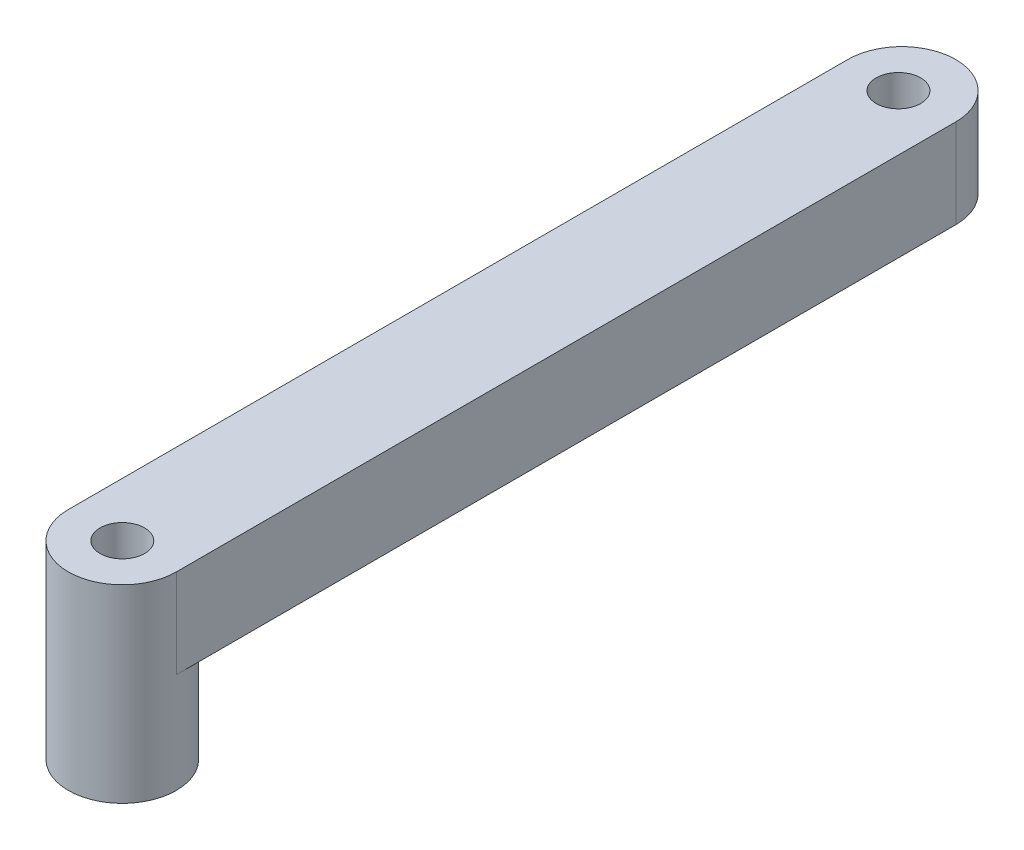
SolidWorks part; units mm, degrees
material "ABS"
ref_plane "Front Plane" through (0, 0, 0) normal (0, 0, 1) x (1, 0, 0)
ref_plane "Top Plane" through (0, 0, 0) normal (0, 1, 0) x (1, 0, 0)
ref_plane "Right Plane" through (0, 0, 0) normal (1, 0, 0) x (0, 0, -1)
sketch "Sketch1" plane through (0, 0, 0) normal (0, 1, 0) x (1, 0, 0)
  circle A0 centre (0, 0) radius 4.85
  circle A1 centre (0, 0) radius 2
  dimension "D1" = 9.7
  dimension "D2" = 4
extrude "Boss-Extrude1" add sketch "Sketch1" along normal blind 9
sketch "Sketch2" plane through (0, 9, 0) normal (0, 1, 0) x (1, 0, 0)
  line L0 (-4.85, 0) -> (-4.85, 70)
  line L2 (4.85, 70) -> (4.85, 0)
  circle A0 centre (0, 0) radius 4.85 construction
  arc A1 (-4.85, 70) -> (4.85, 70) centre (0, 70) cw
  arc A2 (-4.85, 0) -> (4.85, 0) centre (0, 0) ccw
  dimension "D1" = 70
extrude "Boss-Extrude2" add sketch "Sketch2" along normal blind 8
sketch "Sketch4" plane through (0, 9, 0) normal (0, -1, 0) x (1, 0, 0)
  circle A0 centre (0, 0) radius 2
extrude "Cut-Extrude1" cut sketch "Sketch4" against normal blind 10
sketch "Sketch5" plane through (0, 17, 0) normal (0, 1, 0) x (1, 0, 0)
  line L0 (4.85, 0) -> (4.85, 70) construction
  circle A0 centre (-0.15, 69.8523) radius 2
  arc A1 (4.85, 70) -> (-4.85, 70) centre (0, 70) ccw construction
  point P7 (0, 74.85)
  dimension "D1" = 4
  dimension "D2" = 5
  dimension "D3" = 5
extrude "Cut-Extrude2" cut sketch "Sketch5" against normal blind 10
